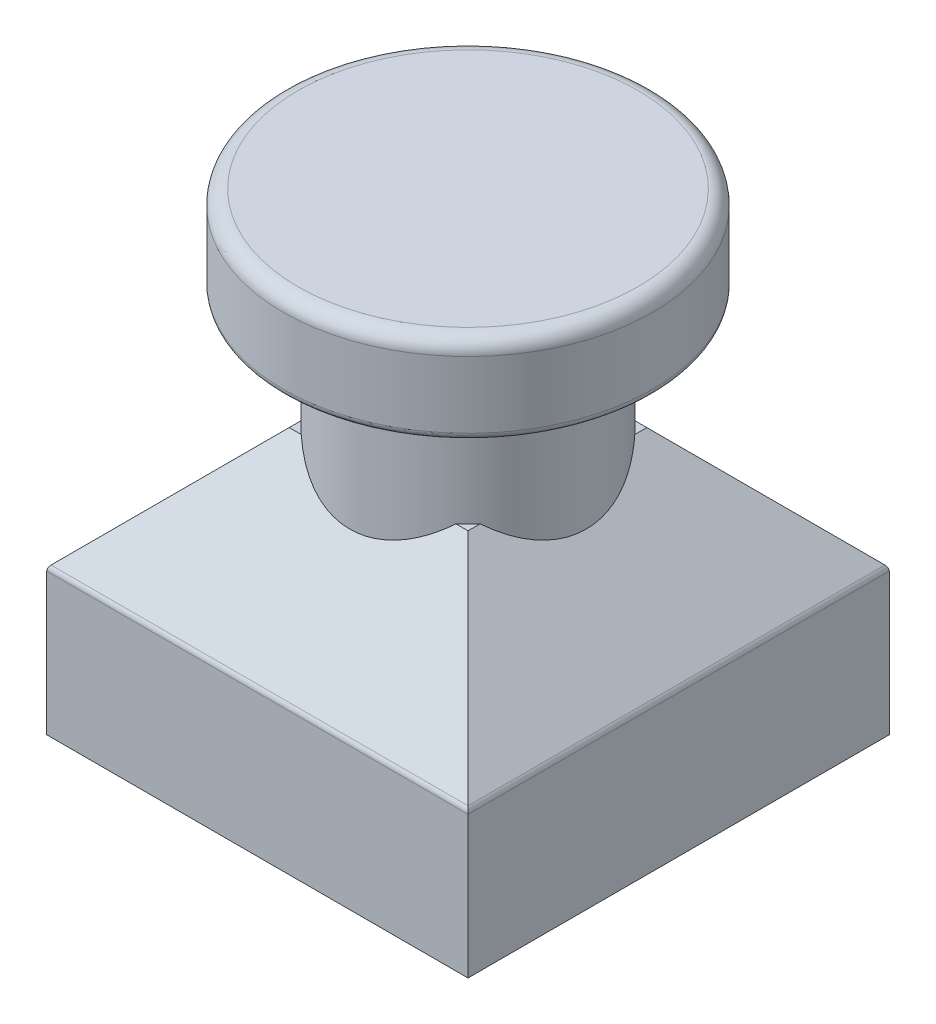
SolidWorks part; units mm, degrees
ref_plane "Ebene vorne" through (0, 0, 0) normal (0, 0, 1) x (1, 0, 0)
ref_plane "Ebene oben" through (0, 0, 0) normal (0, 1, 0) x (1, 0, 0)
ref_plane "Ebene rechts" through (0, 0, 0) normal (1, 0, 0) x (0, 0, -1)
sketch "Skizze1" plane through (0, 0, 0) normal (0, 1, 0) x (1, 0, 0)
  line L0 (-7.125, 0) -> (7.125, 0) construction
  line L1 (-7.125, 7.125) -> (7.125, 7.125)
  line L2 (-7.125, 7.125) -> (-7.125, -7.125)
  line L3 (-7.125, -7.125) -> (7.125, -7.125)
  line L4 (7.125, 7.125) -> (7.125, -7.125)
  line L5 (-7.125, 7.125) -> (7.125, -7.125) construction
  line L6 (-7.125, -7.125) -> (7.125, 7.125) construction
  line L7 (0, 7.125) -> (0, -7.125) construction
  point P0 (0, 0)
  dimension "D1" = 14.25
  dimension "D2" = 14.25
extrude "Aufsatz-Linear austragen1" add sketch "Skizze1" along normal blind 16
sketch "Skizze6" plane through (0, 0, 0) normal (1, 0, 0) x (0, 0, -1)
  line L0 (13.25, 16) -> (13.25, 9)
  line L2 (13.25, 9) -> (4, 9)
  line L3 (4, 9) -> (4, 13)
  line L4 (4, 13) -> (6.25, 13)
  line L5 (6.25, 13) -> (6.25, 16)
  line L6 (7.125, 16) -> (-7.125, 16) construction
  line L7 (6.25, 16) -> (13.25, 16)
  line L8 (0, 0) -> (0, 16)
  line L11 (0, 7.8375) -> (0, -7.8375) construction
  line L12 (0, 0) -> (0, 16) construction
  dimension "D1" = 4
  dimension "D2" = 3
  dimension "D3" = 4
  dimension "D4" = 2.25
revolve "Schnitt-Rotation4" cut sketch "Skizze6" angle 360 about L12 region at (0, 12.2672, -9.0323)
chamfer "Fase1" distance 4.1 angle 45 4 edges at (-7.125, 9, 0) (0, 9, -7.125) (7.125, 9, 0) (0, 9, 7.125)
fillet "Verrundung2" radius 0.5 1 edges at (0, 16, -6.25)
fillet "Verrundung3" radius 0.25 4 edges at (0, 4.9, -7.125) (7.125, 4.9, 0) (0, 4.9, 7.125) (-7.125, 4.9, 0)
fillet "Verrundung4" radius 0.25 1 edges at (0, 13, -6.25)
